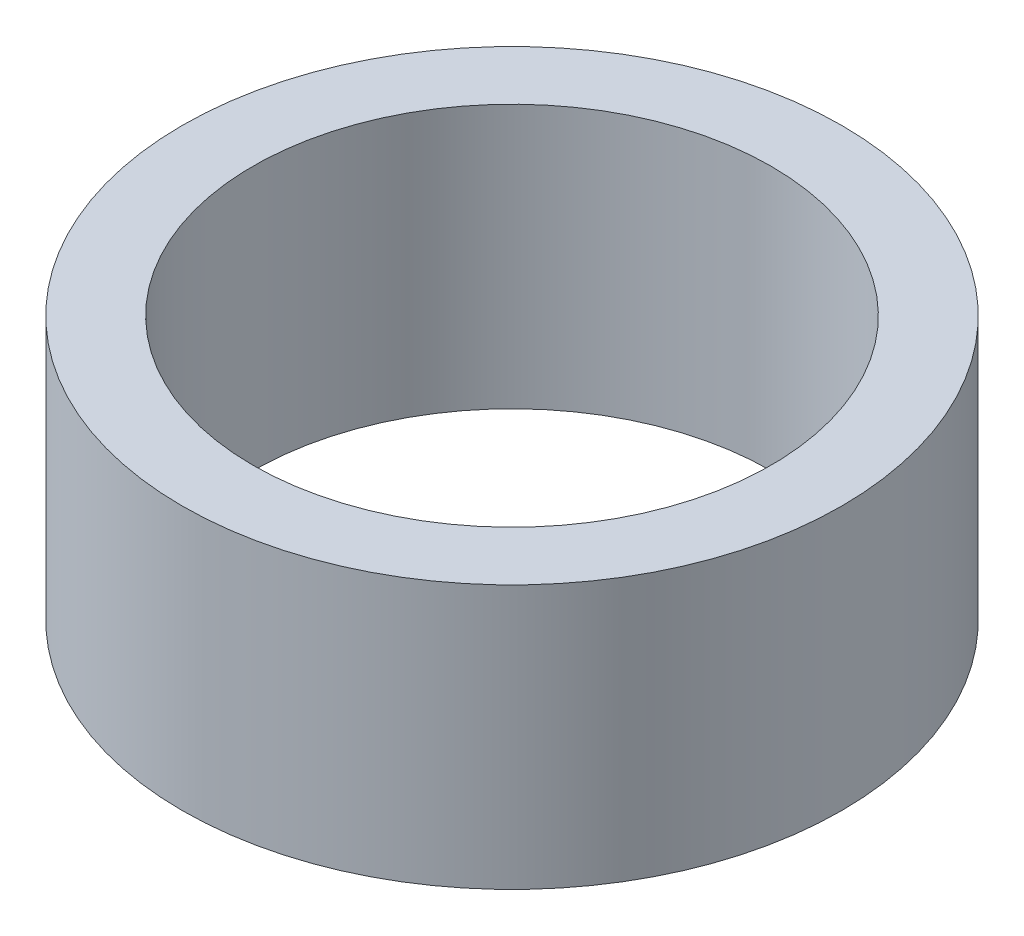
SolidWorks part; units mm, degrees
ref_plane "Front Plane" through (0, 0, 0) normal (0, 0, 1) x (1, 0, 0)
ref_plane "Top Plane" through (0, 0, 0) normal (0, 1, 0) x (1, 0, 0)
ref_plane "Right Plane" through (0, 0, 0) normal (1, 0, 0) x (0, 0, -1)
sketch "Sketch1" plane through (0, 0, 0) normal (0, 1, 0) x (1, 0, 0)
  circle A0 centre (0, 0) radius 35
  dimension "FLANGE_OD" = 70
extrude "Boss-Extrude1" add sketch "Sketch1" along normal blind 28
sketch "Sketch2" plane through (0, 0, 0) normal (0, 1, 0) x (1, 0, 0)
  circle A0 centre (0, 0) radius 27.5
  dimension "BORE_D" = 55
extrude "Cut-Extrude1" cut sketch "Sketch2" along normal through all
sketch "Sketch3" plane through (0, 28, 0) normal (0, 1, 0) x (1, 0, 0)
  circle A0 centre (0, 0) radius 15.1381 construction
  circle A1 centre (-15.1381, 0) radius 1.5
  dimension "BOLT_D" = 3
  dimension "BOLT_PCD" = 30.2761
extrude "Cut-Extrude2" cut sketch "Sketch3" against normal blind 17.8238 rebuild error yes
pattern_circular "CirPattern1" count 5 over 360 rebuild error yes
